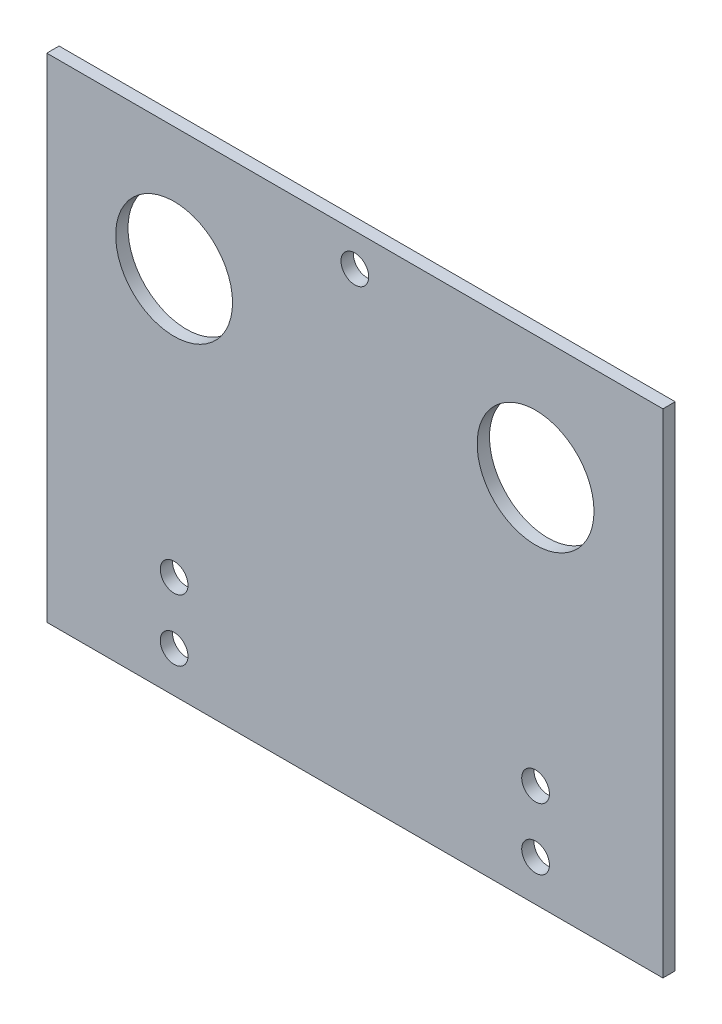
SolidWorks part; units mm, degrees
ref_plane "Front Plane" through (0, 0, 0) normal (0, 0, 1) x (1, 0, 0)
ref_plane "Top Plane" through (0, 0, 0) normal (0, 1, 0) x (1, 0, 0)
ref_plane "Right Plane" through (0, 0, 0) normal (1, 0, 0) x (0, 0, -1)
sketch "Sketch1" plane through (0, 0, 0) normal (0, 0, 1) x (1, 0, 0)
  line L1 (0, 0) -> (150, 0)
  line L2 (0, 0) -> (0, -120)
  line L3 (0, -120) -> (150, -120)
  line L4 (150, 0) -> (150, -120)
  dimension "D1" = 120
  dimension "D2" = 150
extrude "Boss-Extrude1" add sketch "Sketch1" along normal blind 3
sketch "Sketch2" plane through (0, 0, 3) normal (0, 0, 1) x (1, 0, 0)
  line L0 (0, 0) -> (0, -120) construction
  line L1 (150, -120) -> (150, 0) construction
  line L2 (0, -120) -> (150, -120) construction
  line L3 (150, 0) -> (0, 0) construction
  circle A0 centre (31, -30) radius 14.225
  circle A1 centre (119, -30) radius 14.225
  circle A3 centre (31, -110) radius 3.375
  circle A4 centre (119, -110) radius 3.375
  circle A7 centre (75, -8) radius 3.375
  circle A8 centre (31, -95) radius 3.375
  circle A9 centre (119, -95) radius 3.375
  point P10 (60, -8)
  dimension "D1" = 28.45
  dimension "D2" = 28.45
  dimension "D3" = 10
  dimension "D4" = 6.75
  dimension "D5" = 6.75
  dimension "D7" = 6.75
  dimension "D8" = 75
  dimension "D14" = 6.75
  dimension "D17" = 6.75
  dimension "D9" = 31
  dimension "D10" = 31
  dimension "D12" = 30
  dimension "D13" = 8
  dimension "D15" = 15
  dimension "D16" = 15
extrude "Cut-Extrude1" cut sketch "Sketch2" against normal through all
